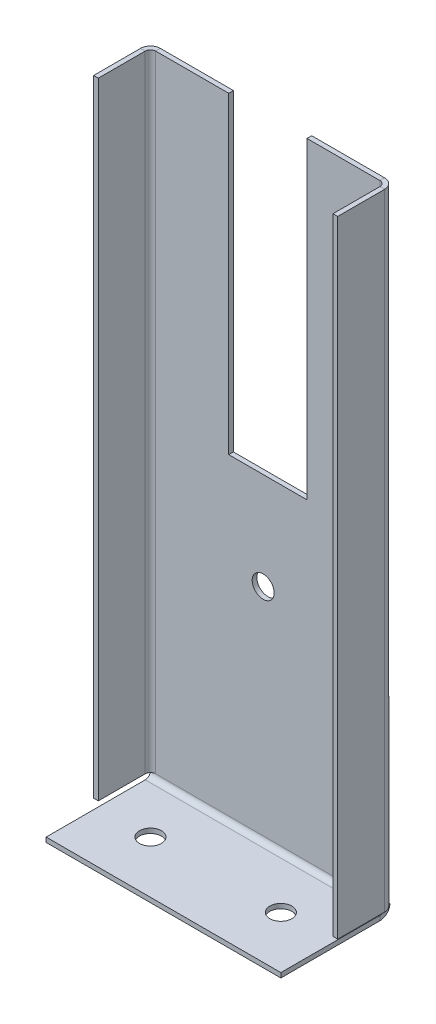
SolidWorks part; units mm, degrees
note: The reader was unsure of these and kept them because the rebuilt part matched: thickness of "Base-Flange2", "Edge-Flange2", "Edge-Flange4", "Edge-Flange5", "Sheet-Metal3", "Sheet-Metal4", "Sheet-Metal5", "Sheet-Metal7", "Sheet-Metal8", "Sheet-Metal10", "Sheet-Metal11"; flange length of "Edge-Flange2", "Edge-Flange4", "Edge-Flange5".
ref_plane "Front Plane" through (0, 0, 0) normal (0, 0, 1) x (1, 0, 0)
ref_plane "Top Plane" through (0, 0, 0) normal (0, 1, 0) x (1, 0, 0)
ref_plane "Right Plane" through (0, 0, 0) normal (1, 0, 0) x (0, 0, -1)
sketch "Sketch1" plane through (0, 0, 0) normal (0, 0, 1) x (1, 0, 0)
  line L1 (-18.337, 75.5286) -> (26.663, 75.5286)
  line L2 (-18.337, 75.5286) -> (-18.337, -44.4714)
  line L3 (-18.337, -44.4714) -> (26.663, -44.4714)
  line L4 (26.663, 75.5286) -> (26.663, -44.4714)
  dimension "D1" = 45
  dimension "D2" = 120
base flange "Base-Flange2" sketch "Sketch1" thickness 0.9 reverse thickness direction no parameters "D1"=1
edge flange "Edge-Flange2" sketch "Sketch16" flange angle 90 flange length 20 flange position bend outside bend radius 1 thickness 0.9 parameters "D1"=3, "D6"=10
sketch "Sketch16" plane through (0, -44.4714, 0) normal (0, -1, 0) x (1, 0, 0)
  line L0 (-18.337, 0) -> (26.663, 0) construction
  line L1 (-18.337, 0) -> (26.663, 0)
  line L2 (-18.337, 0) -> (-18.337, 20)
  line L3 (-18.337, 20) -> (26.663, 20)
  line L4 (26.663, 20) -> (26.663, 0)
bend "EdgeBend2" bend radius 1 bend angle 90 parameters "D5"=1
sketch "Sketch17" plane through (0, 0, 0) normal (0, 0, 1) x (1, 0, 0)
  line L0 (26.663, 75.5286) -> (-18.337, 75.5286) construction
  line L1 (-3.337, 75.5286) -> (11.663, 75.5286)
  line L2 (-3.337, 75.5286) -> (-3.337, 15.5286)
  line L3 (-3.337, 15.5286) -> (11.663, 15.5286)
  line L4 (11.663, 75.5286) -> (11.663, 15.5286)
  line L6 (-18.337, 75.5286) -> (-18.337, -44.4714) construction
  line L7 (26.663, -44.4714) -> (26.663, 75.5286) construction
  dimension "D1" = 60
  dimension "D2" = 15
  dimension "D3" = 15
  dimension "D4" = 15
extrude "Cut-Extrude1" cut sketch "Sketch17" against normal blind 10
edge flange "Edge-Flange4" sketch "Sketch25" flange angle 90 flange length 10 flange position material outside bend radius 1 thickness 0.9 parameters "D1"=3, "D6"=10
sketch "Sketch25" plane through (-18.337, 0, 0) normal (-1, 0, 0) x (0, -1, 0)
  line L2 (-75.5286, 0) -> (-75.5286, 10)
  line L3 (-75.5286, 10) -> (44.4714, 10)
  line L4 (44.4714, 10) -> (44.4714, 0)
  line L5 (-75.5286, 0) -> (44.4714, 0) construction
  line L6 (-75.5286, 0) -> (44.4714, 0)
bend "EdgeBend4" bend radius 1 bend angle 90 parameters "D5"=2
edge flange "Edge-Flange5" sketch "Sketch28" flange angle 90 flange length 10 flange position material outside bend radius 1 thickness 0.9 parameters "D1"=3, "D6"=10
sketch "Sketch28" plane through (26.663, 0, 0) normal (1, 0, 0) x (0, 1, 0)
  line L0 (-44.4714, 0) -> (75.5286, 0) construction
  line L1 (-44.4714, 0) -> (75.5286, 0)
  line L2 (-44.4714, 0) -> (-44.4714, 10)
  line L3 (-44.4714, 10) -> (75.5286, 10)
  line L4 (75.5286, 10) -> (75.5286, 0)
bend "EdgeBend5" bend radius 1 bend angle 90 parameters "D5"=3
hole_wizard "#19 (0.166) Diameter Slot2" positions "Sketch31" profile "Sketch30" size "#19" standard "ANSI Inch" slot yes end condition through all
sketch "Sketch31" plane through (0, -45.4714, 0) normal (0, 1, 0) x (1, 0, 0)
  line L0 (26.663, -1) -> (26.663, -20) construction
  line L1 (26.663, -20) -> (-18.337, -20) construction
  line L2 (-18.337, -20) -> (-18.337, -1) construction
  point P0 (16.663, -10)
  point P2 (-8.337, -10)
  dimension "D1" = 10
  dimension "D2" = 10
  dimension "D3" = 10
  dimension "D4" = 10
sketch "Sketch30" plane through (16.663, -45.4714, 10) normal (1, 0, 0) x (0, 0, 1)
  line L0 (0, 0) -> (0, 0.9)
  line L1 (0, 0.9) -> (2.1082, 0.9)
  line L2 (2.1082, 0.9) -> (2.1082, 0)
  line L5 (2.1082, 0) -> (0, 0)
  line L11 (0, -6.35) -> (0, 107.95) construction
  dimension "Thru Hole Dia." = 4.2164
  dimension "Thru Hole Depth" = 0.9
hole_wizard "#19 (0.166) Diameter Slot1" positions "Sketch33" profile "Sketch32" size "#19" standard "ANSI Inch" slot yes end condition through all
sketch "Sketch33" plane through (0, 0, 0) normal (0, 0, 1) x (1, 0, 0)
  point P5 (3.273, -3.0858)
sketch "Sketch32" plane through (3.273, -3.0858, 0) normal (1, 0, 0) x (0, -1, 0)
  line L0 (0, 0) -> (0, 0.9)
  line L1 (0, 0.9) -> (2.1082, 0.9)
  line L2 (2.1082, 0.9) -> (2.1082, 0)
  line L5 (2.1082, 0) -> (0, 0)
  line L11 (0, -6.35) -> (0, 107.95) construction
  dimension "Thru Hole Dia." = 4.2164
  dimension "Thru Hole Depth" = 0.9
sketch "Bend-Lines3" plane through (0, 0, 0) normal (0, 1, 0) x (1, 0, 0)
sketch "Bounding-Box3" plane through (0, 0, 0) normal (0, 1, 0) x (1, 0, 0)
sheet metal parameters "Sheet-Metal3" thickness 0.9 parameters "D1"=3, "D7"=3
flat pattern "Flat-Pattern3" [suppressed]
sketch "Bend-Lines4" plane through (0, 0, 0) normal (0, 1, 0) x (1, 0, 0)
sketch "Bounding-Box4" [suppressed] plane through (0, 0, 0) normal (0, 1, 0) x (1, 0, 0)
sheet metal parameters "Sheet-Metal4" thickness 0.9 parameters "D1"=3, "D7"=3
flat pattern "Flat-Pattern3" [suppressed]
sketch "Bend-Lines4" plane through (0, 0, 0) normal (0, 1, 0) x (1, 0, 0)
sketch "Bounding-Box4" [suppressed] plane through (0, 0, 0) normal (0, 1, 0) x (1, 0, 0)
bend of the flat pattern "Flatten-<EdgeBend2>1"
sheet metal parameters "Sheet-Metal5" thickness 0.9 parameters "D1"=3, "D7"=3
flat pattern "Flat-Pattern3" [suppressed]
sketch "Bend-Lines4" plane through (0, 0, 0) normal (0, 1, 0) x (1, 0, 0)
sketch "Bounding-Box4" [suppressed] plane through (0, 0, 0) normal (0, 1, 0) x (1, 0, 0)
bend of the flat pattern "Flatten-<EdgeBend2>1"
sheet metal parameters "Sheet-Metal7" thickness 0.9 parameters "D1"=3, "D7"=3
flat pattern "Flat-Pattern3" [suppressed]
sketch "Bend-Lines4" plane through (0, 0, 0) normal (0, 1, 0) x (1, 0, 0)
sketch "Bounding-Box4" [suppressed] plane through (0, 0, 0) normal (0, 1, 0) x (1, 0, 0)
bend of the flat pattern "Flatten-<EdgeBend2>1"
bend of the flat pattern "Flatten-<EdgeBend4>1"
sheet metal parameters "Sheet-Metal8" thickness 0.9 parameters "D1"=3, "D7"=3
flat pattern "Flat-Pattern3" [suppressed]
sketch "Bend-Lines4" plane through (0, 0, 0) normal (0, 1, 0) x (1, 0, 0)
sketch "Bounding-Box4" [suppressed] plane through (0, 0, 0) normal (0, 1, 0) x (1, 0, 0)
bend of the flat pattern "Flatten-<EdgeBend2>1"
bend of the flat pattern "Flatten-<EdgeBend4>1"
bend of the flat pattern "Flatten-<EdgeBend5>1"
sheet metal parameters "Sheet-Metal10" thickness 0.9 parameters "D1"=3, "D7"=3
flat pattern "Flat-Pattern3" [suppressed]
sketch "Bend-Lines4" plane through (0, 0, 0) normal (0, 1, 0) x (1, 0, 0)
sketch "Bounding-Box4" [suppressed] plane through (0, 0, 0) normal (0, 1, 0) x (1, 0, 0)
bend of the flat pattern "Flatten-<EdgeBend2>1"
bend of the flat pattern "Flatten-<EdgeBend4>1"
bend of the flat pattern "Flatten-<EdgeBend5>1"
sheet metal parameters "Sheet-Metal11" thickness 0.9 parameters "D1"=3, "D7"=3
flat pattern "Flat-Pattern3" [suppressed]
sketch "Bend-Lines4" plane through (0, 0, 0) normal (0, 1, 0) x (1, 0, 0)
sketch "Bounding-Box4" [suppressed] plane through (0, 0, 0) normal (0, 1, 0) x (1, 0, 0)
bend of the flat pattern "Flatten-<EdgeBend2>1"
bend of the flat pattern "Flatten-<EdgeBend4>1"
bend of the flat pattern "Flatten-<EdgeBend5>1"
